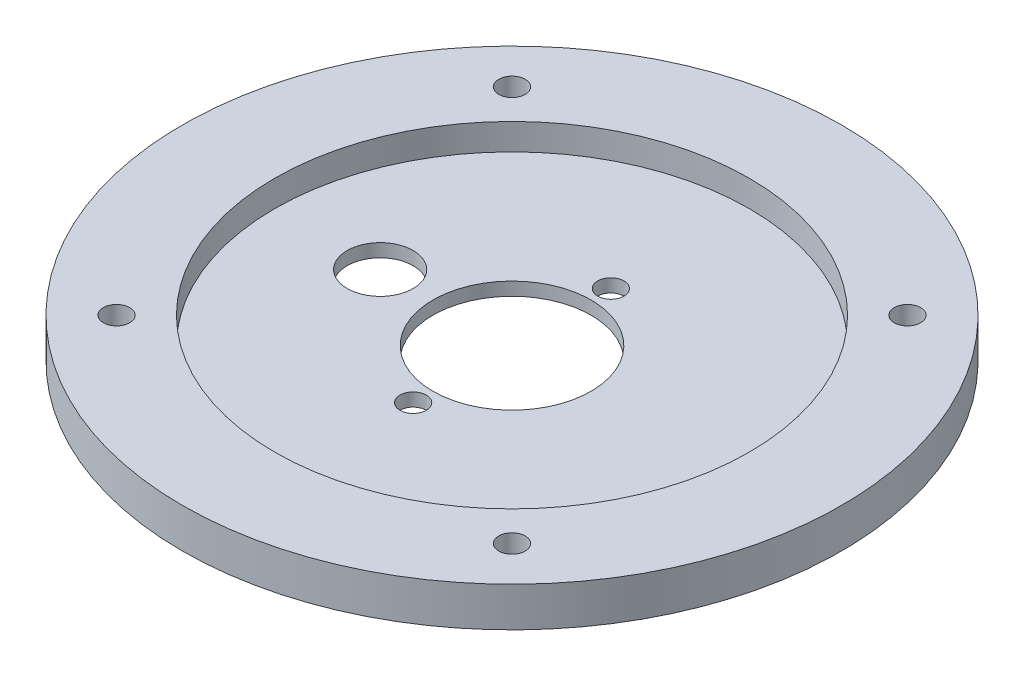
SolidWorks part; units mm, degrees
ref_plane "Front Plane" through (0, 0, 0) normal (0, 0, 1) x (1, 0, 0)
ref_plane "Top Plane" through (0, 0, 0) normal (0, 1, 0) x (1, 0, 0)
ref_plane "Right Plane" through (0, 0, 0) normal (1, 0, 0) x (0, 0, -1)
sketch "Sketch1" plane through (0, 0, 0) normal (0, 1, 0) x (1, 0, 0)
  circle A0 centre (0, 0) radius 25
  dimension "D1" = 50
extrude "Boss-Extrude1" add sketch "Sketch1" along normal blind 3
sketch "Sketch3" plane through (0, 3, 0) normal (0, 1, 0) x (1, 0, 0)
  line L0 (0, -7.5) -> (0, 7.5) construction
  circle A0 centre (0, 0) radius 6
  circle A1 centre (0, 7.5) radius 1
  circle A2 centre (0, -7.5) radius 1
  point P7 (0, 6.6493)
  point P8 (0, 8.5887)
  dimension "D1" = 12
  dimension "D2" = 2
  dimension "D3" = 2
  dimension "D4" = 15
extrude "Cut-Extrude1" cut sketch "Sketch3" against normal through all
sketch "Sketch4" plane through (0, 3, 0) normal (0, 1, 0) x (1, 0, 0)
  line L1 (-15, 15) -> (15, 15) construction
  line L2 (-15, 15) -> (-15, -15) construction
  line L3 (-15, -15) -> (15, -15) construction
  line L4 (15, 15) -> (15, -15) construction
  line L5 (-15, 15) -> (15, -15) construction
  line L6 (-15, -15) -> (15, 15) construction
  circle A0 centre (-15, 15) radius 1
  circle A1 centre (15, 15) radius 1
  circle A2 centre (15, -15) radius 1
  circle A3 centre (-15, -15) radius 1
  point P0 (0, 0)
  point P6 (0, 0)
  dimension "D2" = 2
  dimension "D3" = 4
  dimension "D1" = 30
extrude "Cut-Extrude2" cut sketch "Sketch4" against normal through all
chamfer "Chamfer1" distance 1 angle 45 4 edges at (-15, 0, -14) (15, 0, -14) (15, 0, 16) (-15, 0, 16)
sketch "Sketch5" plane through (0, 3, 0) normal (0, 1, 0) x (1, 0, 0)
  circle A0 centre (0, 0) radius 18
  dimension "D1" = 36
extrude "Cut-Extrude3" cut sketch "Sketch5" against normal blind 2
sketch "Sketch6" plane through (0, 1, 0) normal (0, 1, 0) x (1, 0, 0)
  line L0 (0, 0) -> (-10, 0) construction
  circle A0 centre (-10, 0) radius 2.5
  dimension "D1" = 5
  dimension "D2" = 10
extrude "Cut-Extrude4" cut sketch "Sketch6" against normal through all
